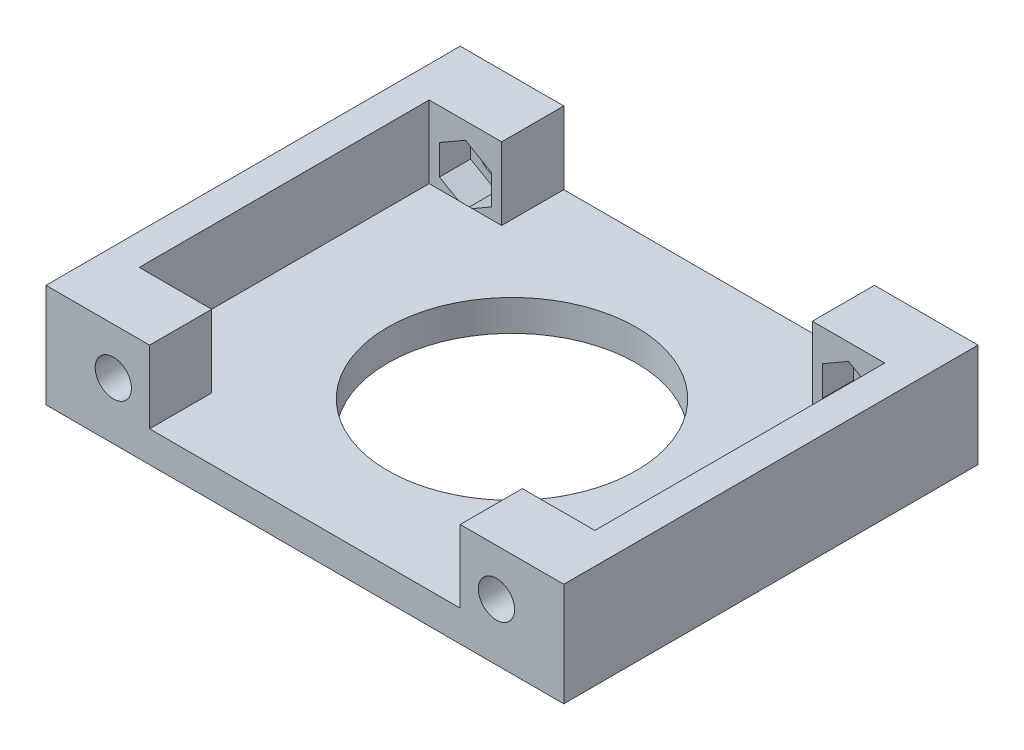
SolidWorks part; units mm, degrees
ref_plane "Front Plane" through (0, 0, 0) normal (0, 0, 1) x (1, 0, 0)
ref_plane "Top Plane" through (0, 0, 0) normal (0, 1, 0) x (1, 0, 0)
ref_plane "Right Plane" through (0, 0, 0) normal (1, 0, 0) x (0, 0, -1)
sketch "Sketch1" plane through (0, 0, 0) normal (0, 1, 0) x (1, 0, 0)
  line L1 (-25, 20) -> (25, 20)
  line L2 (-25, 20) -> (-25, -20)
  line L3 (-25, -20) -> (25, -20)
  line L4 (25, 20) -> (25, -20)
  line L5 (-25, 20) -> (25, -20) construction
  line L6 (-25, -20) -> (25, 20) construction
  point P0 (0, 0)
  dimension "D1" = 50
  dimension "D2" = 40
extrude "Boss-Extrude1" add sketch "Sketch1" along normal blind 3
sketch "Sketch2" plane through (0, 3, 0) normal (0, 1, 0) x (1, 0, 0)
  circle A0 centre (0, 0) radius 12
  dimension "D1" = 24
extrude "Cut-Extrude1" cut sketch "Sketch2" against normal through all
sketch "Sketch3" plane through (0, 3, 0) normal (0, 1, 0) x (1, 0, 0)
  line L0 (-25, -20) -> (25, -20) construction
  line L1 (-25, 20) -> (-22, 20)
  line L2 (-25, 20) -> (-25, -20)
  line L3 (-25, -20) -> (-22, -20)
  line L4 (-22, 20) -> (-22, -20)
  line L6 (22, -20) -> (25, -20)
  line L7 (22, -20) -> (22, 20)
  line L8 (22, 20) -> (25, 20)
  line L9 (25, -20) -> (25, 20)
  dimension "D1" = 3
extrude "Boss-Extrude2" add sketch "Sketch3" along normal blind 7
sketch "Sketch4" plane through (0, 0, 20) normal (0, 0, 1) x (1, 0, 0)
  line L1 (-22, 3) -> (-15, 3)
  line L2 (-22, 3) -> (-22, 10)
  line L3 (-22, 10) -> (-15, 10)
  line L4 (-15, 3) -> (-15, 10)
  line L5 (22, 3) -> (15, 3)
  line L6 (22, 3) -> (22, 10)
  line L7 (22, 10) -> (15, 10)
  line L8 (15, 3) -> (15, 10)
  dimension "D2" = 7
  dimension "6" = 7
extrude "Boss-Extrude3" add sketch "Sketch4" against normal blind 6
sketch "Sketch5" plane through (0, 0, 20) normal (0, 0, 1) x (1, 0, 0)
  line L0 (-18.5, 10) -> (-18.5, 5.5) construction
  line L2 (18.5, 10) -> (18.5, 5.5) construction
  line L3 (-25, 0) -> (25, 0) construction
  line L4 (-18.5, 5.5) -> (18.5, 5.5) construction
  line L6 (-22, 10) -> (-15, 10) construction
  line L7 (-25, 10) -> (-15, 10) construction
  line L8 (15, 10) -> (22, 10) construction
  line L9 (15, 10) -> (15, 3) construction
  line L10 (15, 10) -> (25, 10) construction
  circle A0 centre (-18.5, 5.5) radius 1.75
  circle A1 centre (18.5, 5.5) radius 1.75
  dimension "D1" = 3.5
  dimension "D2" = 3.5
  dimension "D3" = 5.5
extrude "Cut-Extrude2" cut sketch "Sketch5" against normal through all
mirror "Mirror1" about plane through (0, 0, 0) normal (0, 0, 1) of "Cut-Extrude2", "Boss-Extrude3"
sketch "Sketch6" plane through (0, 0, -14) normal (0, 0, 1) x (1, 0, 0)
  line L1 (-18.5, 2.6132) -> (-16, 4.0566)
  line L2 (-16, 4.0566) -> (-16, 6.9434)
  line L3 (-16, 6.9434) -> (-18.5, 8.3868)
  line L4 (-18.5, 8.3868) -> (-21, 6.9434)
  line L5 (-21, 6.9434) -> (-21, 4.0566)
  line L6 (-21, 4.0566) -> (-18.5, 2.6132)
  circle A0 centre (-18.5, 5.5) radius 2.5 construction
  point P1 (-15.7847, 3.9717)
  dimension "D1" = 5
extrude "Cut-Extrude3" cut sketch "Sketch6" against normal blind 3
mirror "Mirror2" about plane through (0, 0, 0) normal (1, 0, 0) of "Cut-Extrude3"
mirror "Mirror3" about plane through (0, 0, 0) normal (0, 0, 1) of "Mirror2"
